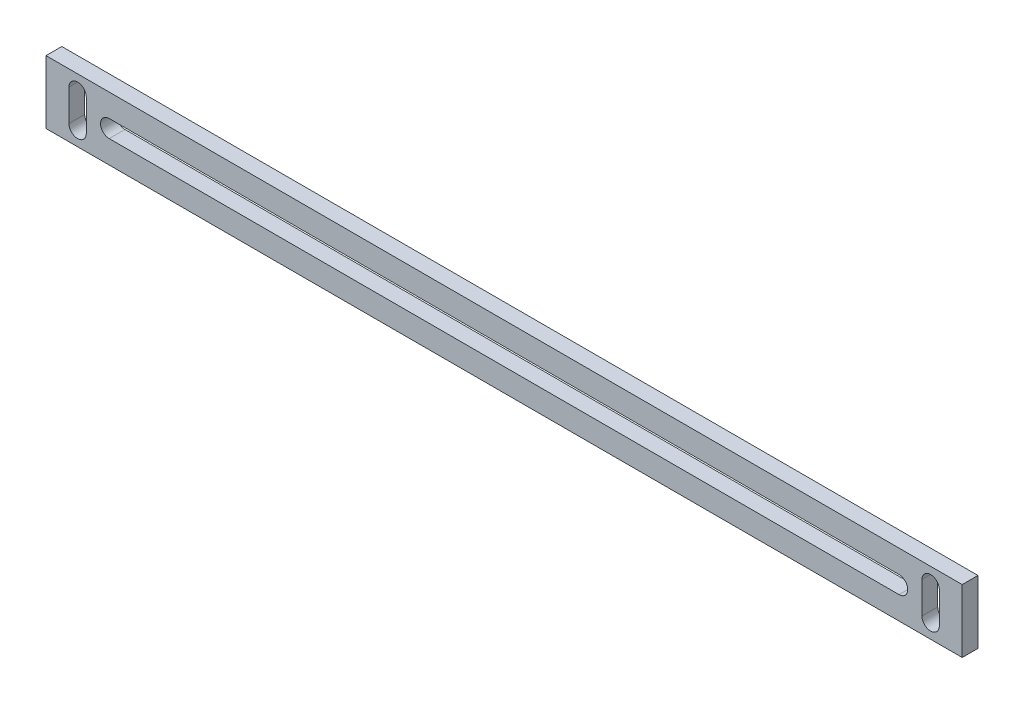
SolidWorks part; units mm, degrees
material "ABS"
ref_plane "前视基准面" through (0, 0, 0) normal (0, 0, 1) x (1, 0, 0)
ref_plane "上视基准面" through (0, 0, 0) normal (0, 1, 0) x (1, 0, 0)
ref_plane "右视基准面" through (0, 0, 0) normal (1, 0, 0) x (0, 0, -1)
other "Configuration Table"
sketch "草图1" plane through (0, 0, 0) normal (0, 0, 1) x (1, 0, 0)
  line L0 (0, 0) -> (0, 10)
  line L1 (0, 10) -> (-145, 10)
  line L2 (-145, 10) -> (-145, -10)
  line L3 (-145, -10) -> (145, -10)
  line L4 (145, -10) -> (145, 10)
  line L5 (145, 10) -> (0, 10)
  dimension "D1" = 290
  dimension "D2" = 20
  dimension "D3" = 10
extrude "凸台-拉伸1" add sketch "草图1" along normal blind 5 contours L4 L5 L1 L2 L3 region at (72.5, 7.0931, 0)
sketch "草图3" plane through (0, 0, 0) normal (0, 0, -1) x (-1, 0, 0)
  line L0 (-145, 0) -> (-135, 0)
  line L1 (-145, -10) -> (-145, 10) construction
  line L2 (-135, 0) -> (-135, 10)
  line L3 (-145, 10) -> (145, 10) construction
  line L4 (-135, 0) -> (-135, -10)
  line L5 (145, -10) -> (-145, -10) construction
  line L6 (-135, 0) -> (-125, 0)
  line L7 (145, 0) -> (135, 0)
  line L8 (145, 10) -> (145, -10) construction
  line L9 (135, 0) -> (135, 10)
  line L10 (135, 0) -> (135, -10)
  line L11 (135, 0) -> (125, 0)
  line L12 (125, 0) -> (-125, 0)
  line L13 (-125, 0) -> (125, 0) construction
  line L14 (-125, 2.75) -> (125, 2.75)
  line L15 (-125, -2.75) -> (125, -2.75)
  line L16 (-135, 0) -> (-135, -5)
  line L17 (-135, -5) -> (-135, 5)
  line L18 (135, -5) -> (135, 5)
  line L19 (-135, -5) -> (-135, 5) construction
  line L20 (-137.75, -5) -> (-137.75, 5)
  line L21 (-132.25, -5) -> (-132.25, 5)
  line L22 (135, -5) -> (135, 5) construction
  line L23 (132.25, -5) -> (132.25, 5)
  line L24 (137.75, -5) -> (137.75, 5)
  arc A0 (-125, 2.75) -> (-125, -2.75) centre (-125, 0) ccw
  arc A1 (125, -2.75) -> (125, 2.75) centre (125, 0) ccw
  arc A2 (-137.75, -5) -> (-132.25, -5) centre (-135, -5) ccw
  arc A3 (-132.25, 5) -> (-137.75, 5) centre (-135, 5) ccw
  arc A4 (132.25, -5) -> (137.75, -5) centre (135, -5) ccw
  arc A5 (137.75, 5) -> (132.25, 5) centre (135, 5) ccw
  point P19 (0, 0)
  point P28 (-135, 0)
  point P33 (135, 0)
  dimension "D1" = 125
  dimension "D2" = 10
  dimension "D3" = 10
  dimension "D4" = 10
extrude "切除-拉伸1" cut sketch "草图3" against normal blind 5 contours L21 A3 L2 L6 | L2 A3 L20 L0 | L20 A2 L4 L0 | L4 A2 L21 L6 | L15 A1 L11 L12 L6 A0 | L11 A1 L14 A0 L6 L12 | L24 A5 L9 L7 | L9 A5 L23 L11 | L23 A4 L10 L11 | L10 A4 L24 L7 region at (136.3123, 3.6062, 0) region at (136.3123, -3.6062, 0) region at (-133.6877, 3.6062, 0) region at (-133.6877, -3.6062, 0) region at (0, 1.3715, 0) region at (0, -1.3715, 0) region at (133.6877, -3.6062, 0) region at (133.6877, 3.6062, 0) region at (-136.3123, 3.6062, 0) region at (-136.3123, -3.6062, 0)
